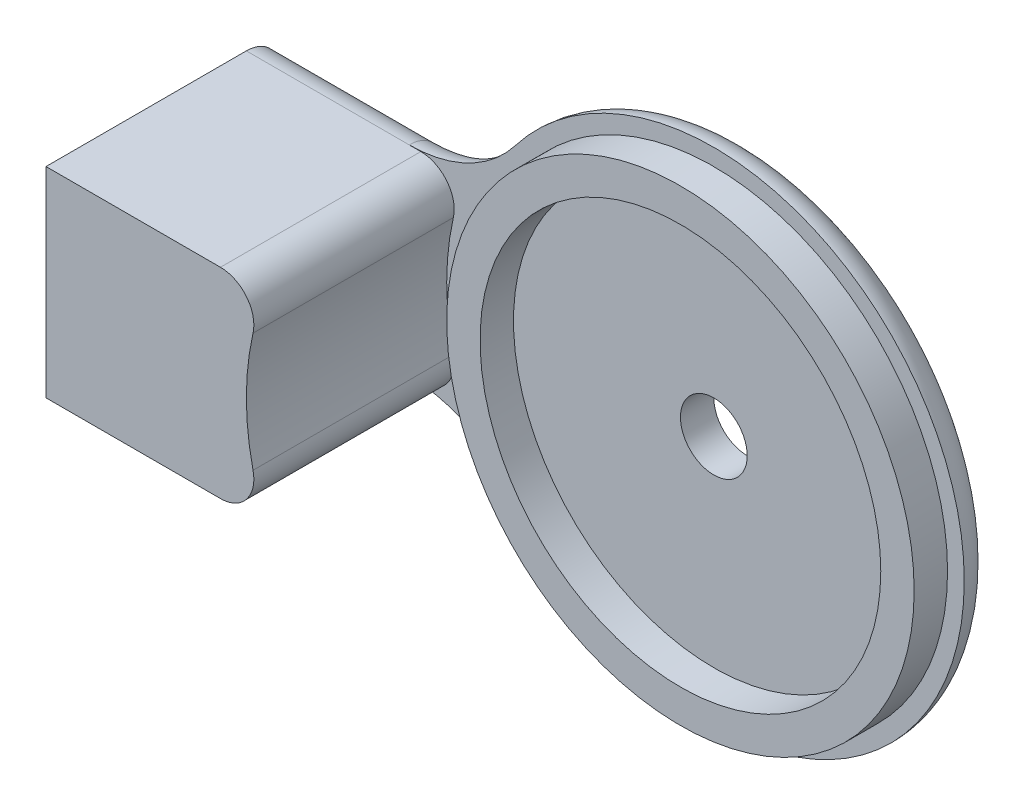
SolidWorks part; units mm, degrees
ref_plane "Plan de face" through (0, 0, 0) normal (0, 0, 1) x (1, 0, 0)
ref_plane "Plan de dessus" through (0, 0, 0) normal (0, 1, 0) x (1, 0, 0)
ref_plane "Plan de droite" through (0, 0, 0) normal (1, 0, 0) x (0, 0, -1)
sketch "Esquisse1" plane through (0, 0, 0) normal (0, 0, 1) x (1, 0, 0)
  line L0 (-1000, 0) -> (49000, 0) construction
  line L1 (-45.6207, 15) -> (-70, 15)
  line L4 (-70, -15) -> (-70, 15)
  line L5 (-45.6207, -15) -> (-70, -15)
  arc A0 (-29.7526, -22.8261) -> (-29.7526, 22.8261) centre (0, 0) ccw
  circle A1 centre (0, 0) radius 5
  arc A2 (-45.6207, 15) -> (-29.7526, 22.8261) centre (-45.6207, 35) ccw
  arc A3 (-45.6207, -15) -> (-29.7526, -22.8261) centre (-45.6207, -35) cw
  point P8 (-34.3693, -15)
  point P9 (-70, 0)
  point P13 (-70, 0)
  point P20 (-34.3693, 15)
  dimension "D1" = 75
  dimension "D4" = 10
  dimension "D5" = 20
  dimension "D2" = 15
  dimension "D3" = 70
extrude "Boss.-Extru.1" add sketch "Esquisse1" along normal blind 5
sketch "Esquisse6" plane through (0, 0, 5) normal (0, 0, 1) x (1, 0, 0)
  circle A0 centre (0, 0) radius 35
  circle A1 centre (0, 0) radius 30
  dimension "D1" = 70
  dimension "D2" = 60
extrude "Boss.-Extru.6" add sketch "Esquisse6" along normal blind 5
sketch "Esquisse8" plane through (0, 0, 5) normal (0, 0, 1) x (1, 0, 0)
  line L1 (-1000, 0) -> (49000, 0) construction
  line L3 (-70, -15) -> (-70, 15)
  line L9 (-70, -15) -> (-43.8748, -15)
  line L10 (-70, 15) -> (-43.8748, 15)
  line L20 (-70, 15) -> (-70, -15) construction
  arc A2 (-38.9998, 8.8889) -> (-38.9998, -8.8889) centre (0, 0) ccw
  arc A3 (-43.8748, 15) -> (-38.9998, 8.8889) centre (-43.8748, 10) cw
  arc A4 (-43.8748, -15) -> (-38.9998, -8.8889) centre (-43.8748, -10) ccw
  point P5 (-70, 0)
  point P15 (-70, 0)
  dimension "D1" = 80
  dimension "D2" = 5
extrude "Boss.-Extru.9" add sketch "Esquisse8" along normal blind 30
fillet "Congé3" radius 5 5 edges at (37.5, 0, 0) (-57.8104, 15, 0) (-57.8104, -15, 0) (-36.7742, -17.0629, 0) (-36.7742, 17.0629, 0)
